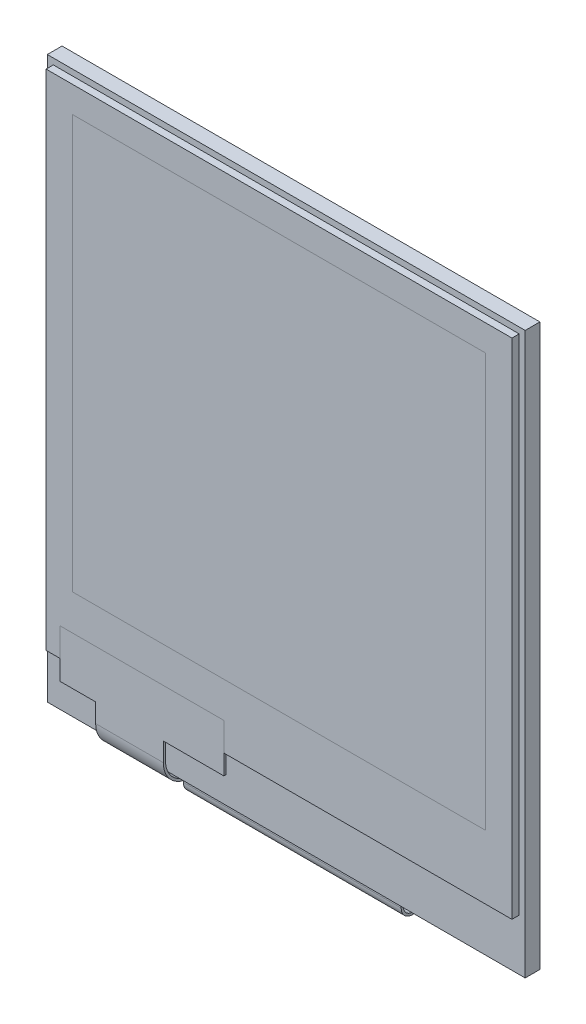
SolidWorks part; units mm, degrees
ref_plane "前视基准面" through (0, 0, 0) normal (0, 0, 1) x (1, 0, 0)
ref_plane "上视基准面" through (0, 0, 0) normal (0, 1, 0) x (1, 0, 0)
ref_plane "右视基准面" through (0, 0, 0) normal (1, 0, 0) x (0, 0, -1)
sketch "草图1" plane through (0, 0, 0) normal (0, 0, 1) x (1, 0, 0)
  line L1 (15.9, -18.66) -> (-15.9, -18.66)
  line L2 (15.9, -18.66) -> (15.9, 18.66)
  line L3 (15.9, 18.66) -> (-15.9, 18.66)
  line L4 (-15.9, -18.66) -> (-15.9, 18.66)
  line L5 (15.9, -18.66) -> (-15.9, 18.66) construction
  line L6 (15.9, 18.66) -> (-15.9, -18.66) construction
  point P0 (0, 0)
  dimension "D1" = 31.8
  dimension "D2" = 37.32
extrude "凸台-拉伸1" add sketch "草图1" along normal blind 0.98
sketch "草图2" plane through (0, 0, 0.98) normal (0, 0, 1) x (1, 0, 0)
  line L0 (0, 18.26) -> (0, 0) construction
  line L1 (-15.5, 18.26) -> (15.5, 18.26)
  line L2 (-15.5, 18.26) -> (-15.5, -15.24)
  line L3 (-15.5, -15.24) -> (15.5, -15.24)
  line L4 (15.5, 18.26) -> (15.5, -15.24)
  line L5 (15.9, 18.66) -> (-15.9, 18.66) construction
  dimension "D1" = 31
  dimension "D2" = 33.5
  dimension "D3" = 0.4
extrude "凸台-拉伸2" add sketch "草图2" along normal blind 1.46 from surface starting at face at (0, 0, 0)
sketch "草图5" plane through (0, 0, 1.46) normal (0, 0, 1) x (1, 0, 0)
  line L0 (-14.57, -15.24) -> (-14.57, -16.56)
  line L1 (-15.5, -15.24) -> (15.5, -15.24) construction
  line L2 (-14.57, -16.56) -> (-12.2, -16.56)
  line L3 (-12.2, -16.56) -> (-12.2, -17.06)
  line L4 (-12.2, -17.06) -> (-7.7, -17.06)
  line L5 (-7.7, -17.06) -> (-7.7, -16.56)
  line L6 (-7.7, -16.56) -> (-3.67, -16.56)
  line L7 (-3.67, -16.56) -> (-3.67, -15.24)
  line L8 (15.5, -15.24) -> (-15.5, -15.24) construction
  line L9 (-3.67, -15.24) -> (-14.57, -15.24)
  line L10 (-15.9, 18.66) -> (-15.9, -18.66) construction
  line L11 (-15.9, -18.66) -> (15.9, -18.66) construction
  point P7 (-14.57, -15.9)
  dimension "D1" = 10.9
  dimension "D2" = 1.33
  dimension "D3" = 3.7
  dimension "D4" = 4.5
  dimension "D5" = 2.1
  dimension "D6" = 0.5
extrude "凸台-拉伸3" add sketch "草图5" against normal blind 0.15
sketch "草图6" plane through (0, 0, 0.98) normal (0, 0, 1) x (1, 0, 0)
  line L0 (-15.9, -18.66) -> (15.9, -18.66) construction
  line L1 (-7.25, -18.66) -> (7.25, -18.66)
  line L2 (-7.25, -18.66) -> (-7.25, -19.16)
  line L3 (-7.25, -19.16) -> (7.25, -19.16)
  line L4 (7.25, -18.66) -> (7.25, -19.16)
  line L5 (0, 0) -> (0, -18.66) construction
  dimension "D1" = 14.5
  dimension "D2" = 0.5
extrude "凸台-拉伸4" add sketch "草图6" against normal blind 0.15 from offset 0.4 offset against normal yes
sketch "草图7" plane through (0, 0, 1.46) normal (0, 0, 1) x (1, 0, 0)
  line L0 (0, 2.765) -> (0, 0) construction
  line L1 (13.755, -10.99) -> (-13.755, -10.99)
  line L2 (13.755, -10.99) -> (13.755, 16.52)
  line L3 (13.755, 16.52) -> (-13.755, 16.52)
  line L4 (-13.755, -10.99) -> (-13.755, 16.52)
  line L5 (13.755, -10.99) -> (-13.755, 16.52) construction
  line L6 (13.755, 16.52) -> (-13.755, -10.99) construction
  line L7 (15.9, 18.66) -> (-15.9, 18.66) construction
  point P0 (0, 2.765)
  dimension "D1" = 27.51
  dimension "D2" = 2.14
wrap "包覆1" sketch "草图7" wrap type scribe source sketch "草图7"
sketch "草图9" plane through (0, 0, 1.46) normal (0, 0, 1) x (1, 0, 0)
  line L0 (-14.57, -15.24) -> (-14.57, -13.36)
  line L1 (-14.57, -13.36) -> (-3.67, -13.36)
  line L2 (-3.67, -13.36) -> (-3.67, -15.24)
  line L3 (-3.67, -16.56) -> (-3.67, -15.24) construction
  line L4 (-7.7, -16.56) -> (-3.67, -16.56) construction
  line L5 (-7.7, -17.06) -> (-7.7, -16.56) construction
  line L6 (-12.2, -17.06) -> (-7.7, -17.06) construction
  line L7 (-12.2, -16.56) -> (-12.2, -17.06) construction
  line L8 (-14.57, -16.56) -> (-12.2, -16.56) construction
  line L9 (-14.57, -15.24) -> (-14.57, -16.56) construction
  line L10 (-3.67, -16.56) -> (-3.67, -15.24)
  line L11 (-7.7, -16.56) -> (-3.67, -16.56)
  line L12 (-7.7, -17.06) -> (-7.7, -16.56)
  line L13 (-12.2, -17.06) -> (-7.7, -17.06)
  line L14 (-12.2, -16.56) -> (-12.2, -17.06)
  line L15 (-14.57, -16.56) -> (-12.2, -16.56)
  line L16 (-14.57, -15.24) -> (-14.57, -16.56)
  dimension "D1" = 3.2
wrap "包覆2" sketch "草图9" wrap type scribe source sketch "草图9"
sketch "草图10" plane through (-12.2, 0, 0) normal (-1, 0, 0) x (0, 0, 1)
  line L0 (1.46, -17.06) -> (1.46, -17.81)
  line L1 (-2.04, -17.81) -> (-2.04, -17.31)
  line L2 (0.98, -18.66) -> (0, -18.66) construction
  arc A0 (1.46, -17.81) -> (-2.04, -17.81) centre (-0.29, -17.81) cw
  dimension "D2" = 1.75
  dimension "D1" = 0.75
  dimension "D3" = 1.35
extrude "拉伸-薄壁1" add sketch "草图10" against normal up to surface (4.5 mm away) thin thin type one direction wall 0.15
sketch "草图11" plane through (0, 0, -2.04) normal (0, 0, -1) x (-1, 0, 0)
  line L0 (7.7, -17.31) -> (7.7, -11.31)
  line L1 (7.7, -11.31) -> (9.7, -11.31)
  line L2 (9.7, -11.31) -> (9.7, -8.81)
  line L3 (9.7, -8.81) -> (12.2, -8.81)
  line L4 (12.2, -8.81) -> (12.2, -3.81)
  line L5 (12.2, -3.81) -> (15.7, -3.81)
  line L6 (15.7, -3.81) -> (15.7, -8.81)
  line L7 (15.7, -8.81) -> (18.2, -8.81)
  line L8 (18.2, -8.81) -> (18.2, -15.01)
  line L9 (18.2, -15.01) -> (16.2, -15.01)
  line L10 (16.2, -15.01) -> (16.2, -17.31)
  line L11 (16.2, -17.31) -> (7.7, -17.31)
  dimension "D1" = 8.5
  dimension "D2" = 10.5
  dimension "D3" = 2.3
  dimension "D4" = 6
  dimension "D5" = 8.5
  dimension "D6" = 8.5
  dimension "D7" = 13.5
  dimension "D8" = 3.5
  dimension "D9" = 2.5
extrude "凸台-拉伸5" add sketch "草图11" against normal blind 0.15
sketch "草图12" plane through (-7.25, 0, 0) normal (-1, 0, 0) x (0, 0, 1)
  line L0 (-2.04, -11.1434) -> (-2.04, -7.66)
  line L1 (0.58, -18.66) -> (0.58, -19.16) construction
  line L2 (0.98, -18.66) -> (0, -18.66) construction
  line L3 (-2.04, -17.31) -> (-2.04, -15.01) construction
  arc A0 (0.58, -19.16) -> (-0.8913, -19.3656) centre (-0.17, -19.16) cw
  arc A1 (-0.8913, -19.3656) -> (-2.04, -11.1434) centre (27.96, -11.1434) cw
  point P9 (-1.5792, -14.4516)
  dimension "D1" = 0.75
  dimension "D2" = 30
  dimension "D3" = 11
extrude "拉伸-薄壁2" add sketch "草图12" against normal up to surface (14.5 mm away) thin up to face at (7.25, -18.91, 0.505) thin type one direction wall 0.15
sketch "草图13" plane through (0, 0, -2.04) normal (0, 0, -1) x (-1, 0, 0)
  line L1 (-7.25, -7.66) -> (-5.25, -7.66)
  line L2 (-7.25, -7.66) -> (-7.25, -15.66)
  line L3 (-7.25, -15.66) -> (-5.25, -15.66)
  line L4 (-5.25, -7.66) -> (-5.25, -15.66)
  line L5 (7.25, -7.66) -> (5.25, -7.66)
  line L6 (7.25, -7.66) -> (7.25, -15.66)
  line L7 (7.25, -15.66) -> (5.25, -15.66)
  line L8 (5.25, -7.66) -> (5.25, -15.66)
  dimension "D1" = 10.5
  dimension "D2" = 8
extrude "切除-拉伸2" cut sketch "草图13" against normal up to next
